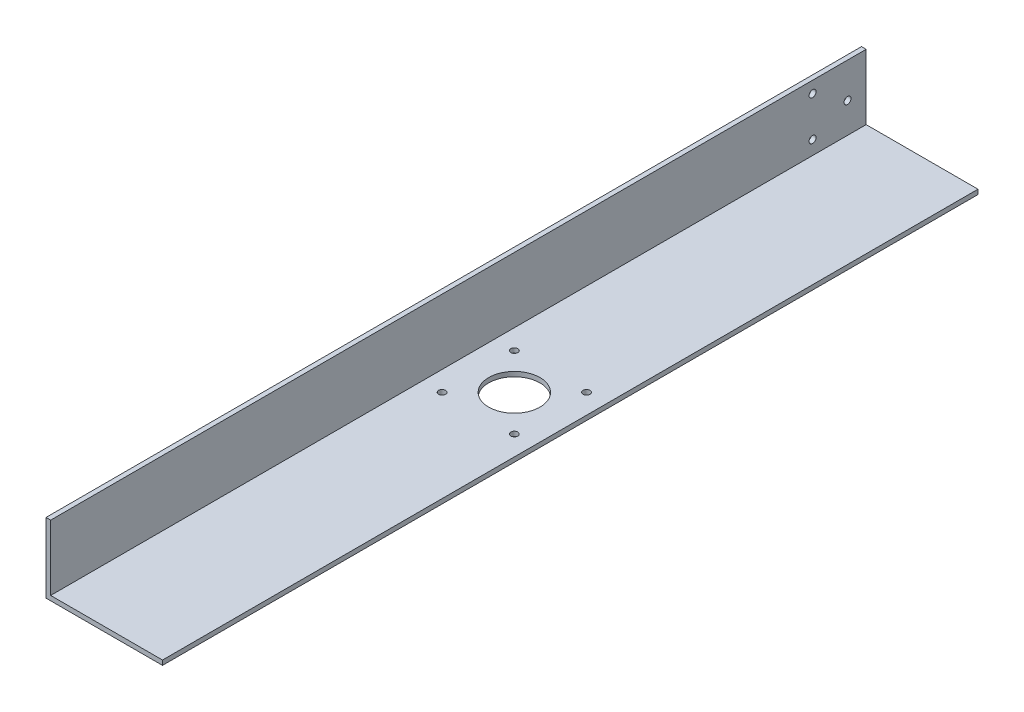
SolidWorks part; units mm, degrees
ref_plane "Front Plane" through (0, 0, 0) normal (0, 0, 1) x (1, 0, 0)
ref_plane "Top Plane" through (0, 0, 0) normal (0, 1, 0) x (1, 0, 0)
ref_plane "Right Plane" through (0, 0, 0) normal (1, 0, 0) x (0, 0, -1)
sketch "Sketch1" plane through (0, 0, 0) normal (0, 0, 1) x (1, 0, 0)
  line L0 (0, 0) -> (0, 30)
  line L1 (0, 30) -> (2, 30)
  line L2 (2, 30) -> (2, 2)
  line L3 (2, 2) -> (50, 2)
  line L4 (50, 2) -> (50, 0)
  line L5 (50, 0) -> (0, 0)
extrude "Boss-Extrude1" add sketch "Sketch1" along normal up to surface (350 mm away)
sketch "Sketch7" plane through (0, 2, 0) normal (0, 1, 0) x (1, 0, 0)
  circle A0 centre (26, -175) radius 11
  point P7 (2, -350)
extrude "Cut-Extrude1" cut sketch "Sketch7" against normal through all from surface starting at face at (26, 2, 175)
sketch "Sketch8" plane through (0, 2, 0) normal (0, 1, 0) x (1, 0, 0)
  circle A0 centre (41.5, -190.5) radius 1.5
  circle A1 centre (41.5, -159.5) radius 1.5
  circle A2 centre (10.5, -190.5) radius 1.5
  circle A3 centre (10.5, -159.5) radius 1.5
extrude "Cut-Extrude2" cut sketch "Sketch8" against normal through all
hole_wizard "Ø3.0 (3) Diameter Hole1" positions "Sketch9" profile "Sketch10" hole size "Ø3.0" standard "ISO"
sketch "Sketch9" plane through (0, 182.32, 128.862) normal (-1, 0, 0) x (0, 0, -1)
  point P0 (105.862, 174.32)
  point P2 (105.862, 157.32)
  point P4 (120.862, 167.32)
  point P8 (0, 0)
  point P9 (0, 0)
  point P10 (0, 0)
sketch "Sketch10" plane through (0, 8, 23) normal (0, 1, 0) x (0, 0, 1)
  line L0 (0, 0) -> (0, 1.999)
  line L1 (0, 1.999) -> (1.5, 1.999)
  line L2 (1.5, 1.999) -> (1.5, 0)
  line L3 (1.5, 0) -> (0, 0)
  line L4 (0, -6.35) -> (0, 107.95) construction
  dimension "Thru Hole Dia." = 3
  dimension "Thru Hole Depth" = 1.999
